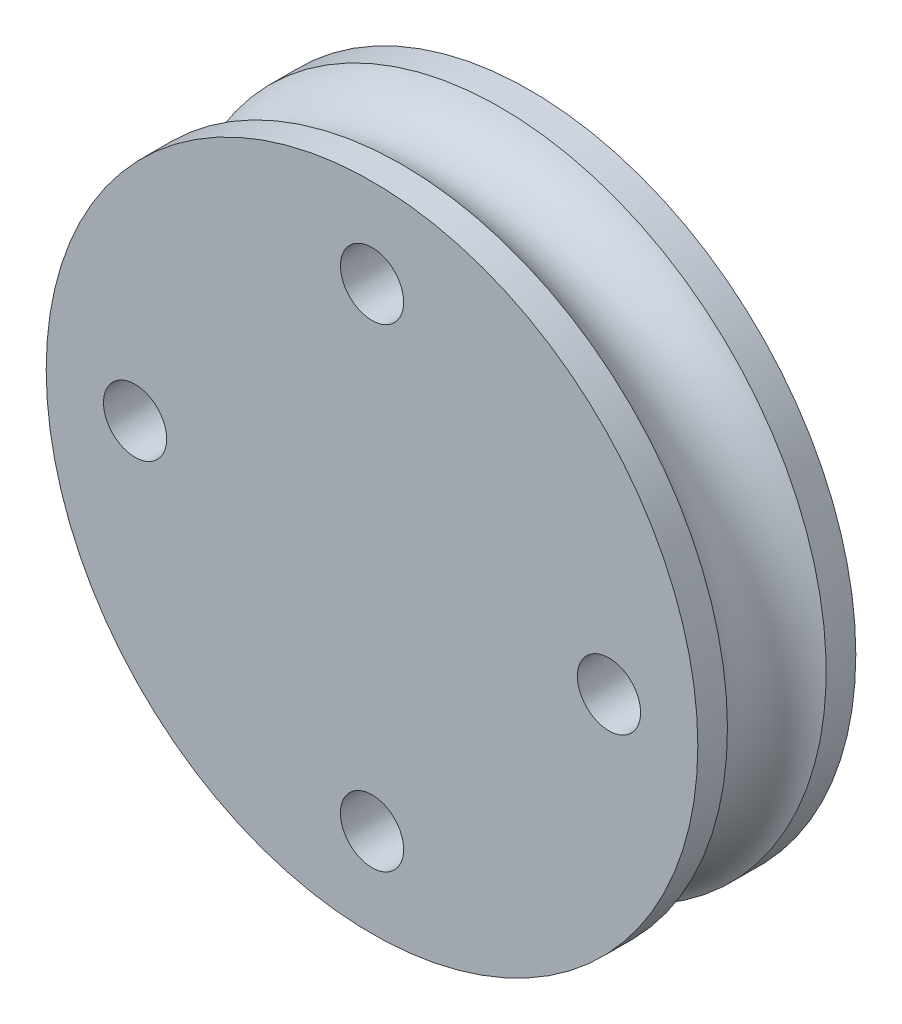
SolidWorks part; units mm, degrees
ref_plane "Ebene vorne" through (0, 0, 0) normal (0, 0, 1) x (1, 0, 0)
ref_plane "Ebene oben" through (0, 0, 0) normal (0, 1, 0) x (1, 0, 0)
ref_plane "Ebene rechts" through (0, 0, 0) normal (1, 0, 0) x (0, 0, -1)
sketch "Skizze2" plane through (0, 0, 0) normal (0, 0, 1) x (1, 0, 0)
  circle A1 centre (6.0006, 0.0004) radius 0.8
  circle A2 centre (0.0006, 6.0004) radius 0.8
  circle A3 centre (-5.9994, 0.0004) radius 0.8
  circle A4 centre (0.0006, -5.9996) radius 0.8
  circle A5 centre (0, 0) radius 8.25
  dimension "D1" = 16.5
  dimension "D2" = 1.6
extrude "Aufsatz-Linear austragen1" add sketch "Skizze2" along normal blind 4
sketch "Skizze3" plane through (0, 0, 4) normal (0, 0, 1) x (1, 0, 0)
  circle A0 centre (0.0006, 6.0004) radius 1.9 construction
  circle A1 centre (-5.9994, 0.0004) radius 1.9 construction
  circle A2 centre (0.0006, -5.9996) radius 1.9 construction
  circle A3 centre (6.0006, 0.0004) radius 1.9 construction
  dimension "D1" = 3.8
  dimension "D2" = 3.8
  dimension "D3" = 3.8
  dimension "D4" = 3.8
sketch "Skizze5" plane through (0, 0, 0) normal (1, 0, 0) x (0, 0, -1)
  line L1 (0, 8.25) -> (-4, 8.25) construction
  line L2 (-3.25, 8.25) -> (-0.75, 8.25)
  line L4 (-2, 0) -> (-2, 8.25) construction
  line L5 (8.5813, 0) -> (-8.5813, 0) construction
  line L6 (-3.25, 8.25) -> (-4, 8.25) construction
  line L7 (-0.75, 8.25) -> (0, 8.25) construction
  line L8 (0, 9.3044) -> (0, -9.3044) construction
  line L9 (-2, 0) -> (-5.4189, 0) construction
  arc A1 (-3.25, 8.25) -> (-0.75, 8.25) centre (-2, 8.8805) ccw
  dimension "D1" = 1.4
  dimension "D2" = 2.5
revolve "Schnitt-Rotation4" cut sketch "Skizze5" angle 360 about L9
